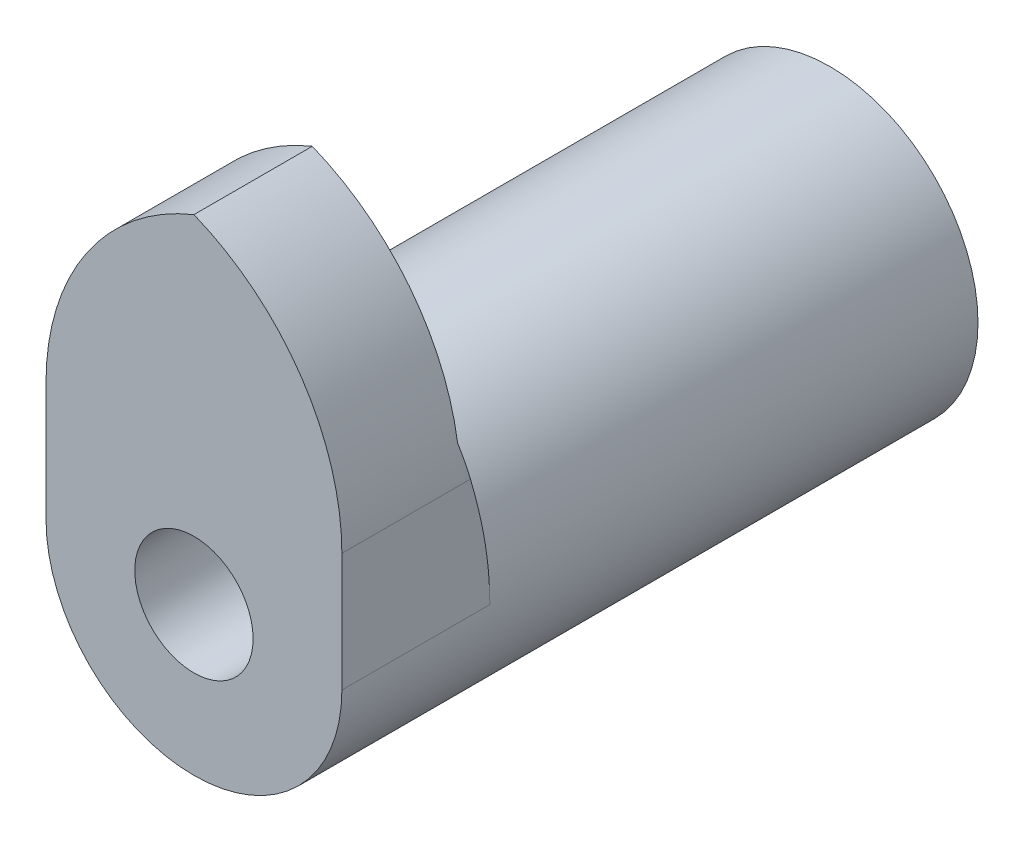
SolidWorks part; units mm, degrees
material "ABS"
ref_plane "Płaszczyzna przednia" through (0, 0, 0) normal (0, 0, 1) x (1, 0, 0)
ref_plane "Płaszczyzna górna" through (0, 0, 0) normal (0, 1, 0) x (1, 0, 0)
ref_plane "Płaszczyzna prawa" through (0, 0, 0) normal (1, 0, 0) x (0, 0, -1)
sketch "Szkic1" plane through (0, 0, 0) normal (0, 0, 1) x (1, 0, 0)
  circle A0 centre (0, 0) radius 2
  circle A1 centre (0, 0) radius 5
  dimension "D1" = 4
  dimension "D2" = 10
extrude "Dodanie-wyciągnięcie1" add sketch "Szkic1" along normal blind 21.5
sketch "Szkic2" plane through (0, 0, 21.5) normal (0, 0, 1) x (1, 0, 0)
  line L0 (-5, 0) -> (-5, 12)
  line L1 (-5, 12) -> (5, 12)
  line L2 (5, 12) -> (5, 0)
  circle A0 centre (0, 0) radius 5 construction
  circle A1 centre (0, 0) radius 5
  circle M5 centre (0, 0) radius 5
  dimension "D4" = 10
  dimension "D1" = 12
  dimension "D2" = 10
  dimension "D3" = 5
extrude "Dodanie-wyciągnięcie2" add sketch "Szkic2" against normal blind 4 contours L2 L1 L0 M5 region at (0, 7.8864, 21.5)
chamfer "Sfazowanie1" distance 1 angle 65 1 edges at (0, 5, 17.5) first distance on face at (5, 0, 0)
fillet "Zaokrąglenie1" radius 8 2 edges at (-5, 12, 19.5) (5, 12, 19.5)
